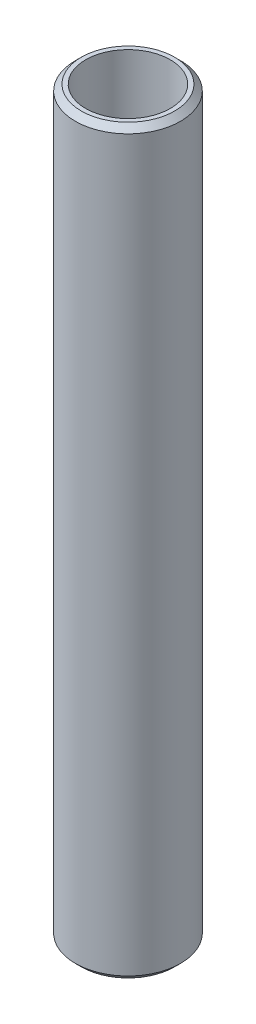
SolidWorks part; units mm, degrees
ref_plane "Front Plane" through (0, 0, 0) normal (0, 0, 1) x (1, 0, 0)
ref_plane "Top Plane" through (0, 0, 0) normal (0, 1, 0) x (1, 0, 0)
ref_plane "Right Plane" through (0, 0, 0) normal (1, 0, 0) x (0, 0, -1)
sketch "Sketch1" plane through (0, 0, 0) normal (0, 1, 0) x (1, 0, 0)
  circle A0 centre (0, 0) radius 40
  dimension "SHAFT_OD" = 80
extrude "Boss-Extrude1" add sketch "Sketch1" along normal blind 563.7325
sketch "Sketch2" plane through (0, 0, 0) normal (0, 1, 0) x (1, 0, 0)
  circle A0 centre (0, 0) radius 32.1634
  dimension "BORE_D" = 64.3267
extrude "Cut-Extrude1" cut sketch "Sketch2" along normal through all
chamfer "Chamfer1" distance 4.496 angle 45 2 edges at (0, 563.7325, 40) (0, 0, 40)
